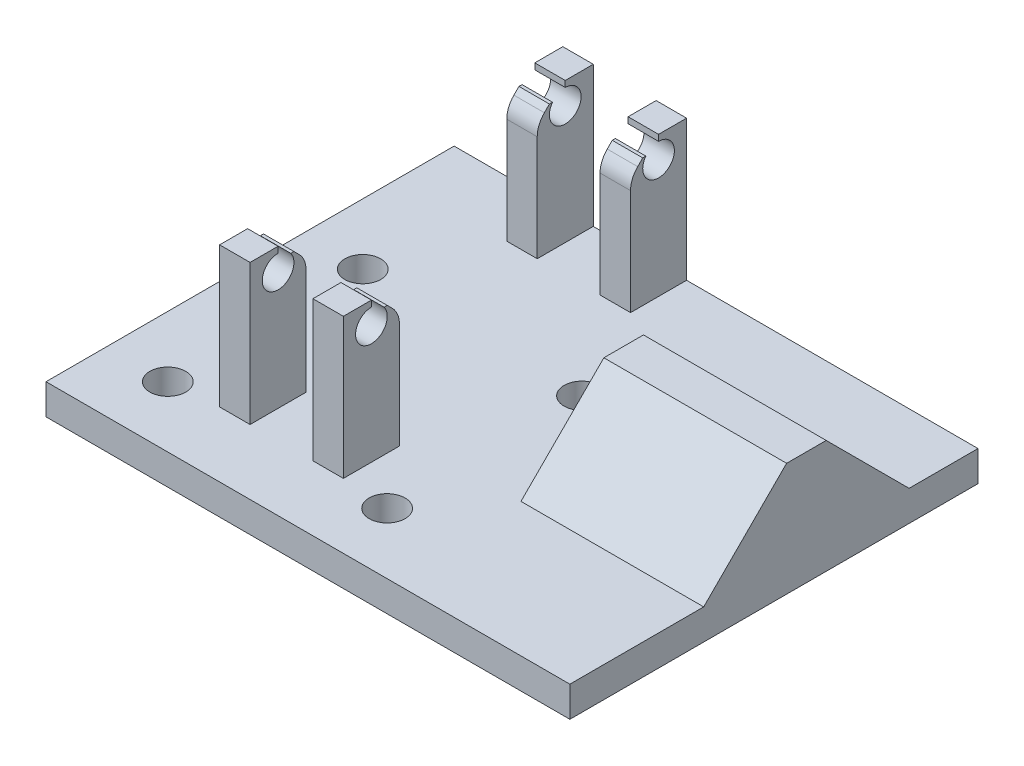
SolidWorks part; units mm, degrees
ref_plane "Front Plane" through (0, 0, 0) normal (0, 0, 1) x (1, 0, 0)
ref_plane "Top Plane" through (0, 0, 0) normal (0, 1, 0) x (1, 0, 0)
ref_plane "Right Plane" through (0, 0, 0) normal (1, 0, 0) x (0, 0, -1)
sketch "Sketch1" plane through (0, 0, 0) normal (0, 1, 0) x (1, 0, 0)
  line L1 (0, 0) -> (56, 0)
  line L2 (0, 0) -> (0, 67)
  line L3 (0, 67) -> (56, 67)
  line L4 (56, 0) -> (56, 67)
  line L5 (10, 42) -> (46, 42) construction
  line L6 (10, 42) -> (10, 10) construction
  line L7 (10, 10) -> (46, 10) construction
  line L8 (46, 42) -> (46, 10) construction
  circle A0 centre (10, 42) radius 2.95
  circle A1 centre (46, 42) radius 2.95
  circle A2 centre (46, 10) radius 2.95
  circle A3 centre (10, 10) radius 2.95
  dimension "D7" = 5.9
  dimension "D1" = 36
  dimension "D2" = 32
  dimension "D3" = 10
  dimension "D4" = 10
  dimension "D5" = 10
  dimension "D6" = 25
extrude "Boss-Extrude1" add sketch "Sketch1" along normal blind 5
sketch "Sketch2" plane through (56, 0, 0) normal (1, 0, 0) x (0, 0, -1)
  line L0 (0, 5) -> (67, 5) construction
  line L1 (17.3475, 26) -> (19.86, 26)
  line L4 (10.66, 5) -> (19.86, 5)
  line L5 (19.86, 26) -> (19.86, 5)
  line L11 (38.83, 4.2222) -> (38.83, 17.2936) construction
  line L12 (15.26, 5) -> (15.26, 13.3475) construction
  line L13 (62.4, 28.05) -> (67, 28.05)
  line L14 (15.26, 28.05) -> (10.66, 28.05)
  line L16 (15.26, 28.05) -> (15.26, 27.05)
  line L17 (10.66, 28.05) -> (10.66, 5)
  line L18 (62.4, 28.05) -> (62.4, 27.05)
  line L19 (60.3125, 26) -> (57.8, 26)
  line L20 (57.8, 26) -> (57.8, 5)
  line L21 (67, 5) -> (57.8, 5)
  line L22 (67, 28.05) -> (67, 5)
  line L23 (67, 5) -> (67, 0) construction
  arc A3 (15.26, 27.05) -> (17.3475, 26) centre (15.26, 24.45) ccw
  arc A4 (62.4, 27.05) -> (60.3125, 26) centre (62.4, 24.45) cw
  point P8 (0, 0)
  point P14 (0, 0)
  point P15 (15.26, 5)
  point P17 (0, 0)
  point P23 (0, 0)
  point P27 (0, 0)
  point P28 (25.36, 27.95)
  point P29 (0, 0)
  dimension "D2" = 23.57
  dimension "D1" = 2.6
  dimension "D3" = 2
  dimension "D5" = 19.45
  dimension "D4" = 21
  dimension "D6" = 1
extrude "Boss-Extrude2" add sketch "Sketch2" along normal blind 5 from offset 22.84 offset against normal yes
chamfer "Chamfer2" distance 2 angle 45 2 edges at (35.66, 26, -19.86) (35.66, 26, -57.8)
fillet "Fillet1" radius 4 2 edges at (35.66, 24, -57.8) (35.66, 24, -19.86)
ref_plane "Plane1" through (28, 0, 0) normal (-1, 0, 0) x (0, 0, 1)
mirror "Mirror1" about plane through (28, 0, 0) normal (-1, 0, 0) of "Fillet1", "Chamfer2", "Boss-Extrude2"
sketch "Sketch3" plane through (0, 5, 0) normal (0, 1, 0) x (1, 0, 0)
  line L0 (0, 0) -> (56, 0) construction
  line L1 (56, 67) -> (86, 67)
  line L2 (56, 67) -> (56, 0)
  line L3 (56, 0) -> (86, 0)
  line L4 (86, 67) -> (86, 0)
  dimension "D1" = 30
extrude "Boss-Extrude3" add sketch "Sketch3" against normal up to surface (5 mm away) up to face at (46, 0, -7.05)
sketch "Sketch4" plane through (0, 5, 0) normal (0, 1, 0) x (1, 0, 0)
  line L0 (38.16, 57.8) -> (33.16, 57.8) construction
  line L1 (56, 42.08) -> (86, 42.08)
  line L2 (56, 42.08) -> (56, 35.58)
  line L3 (56, 35.58) -> (86, 35.58)
  line L4 (86, 42.08) -> (86, 35.58)
  line L6 (86, 0) -> (86, 67) construction
  dimension "D1" = 6.5
  dimension "D2" = 15.72
  dimension "D3" = 30
extrude "Boss-Extrude4" add sketch "Sketch4" along normal blind 13.61
chamfer "Chamfer3" distance 13.61 angle 45 2 edges at (71, 5, -35.58) (71, 5, -42.08)
